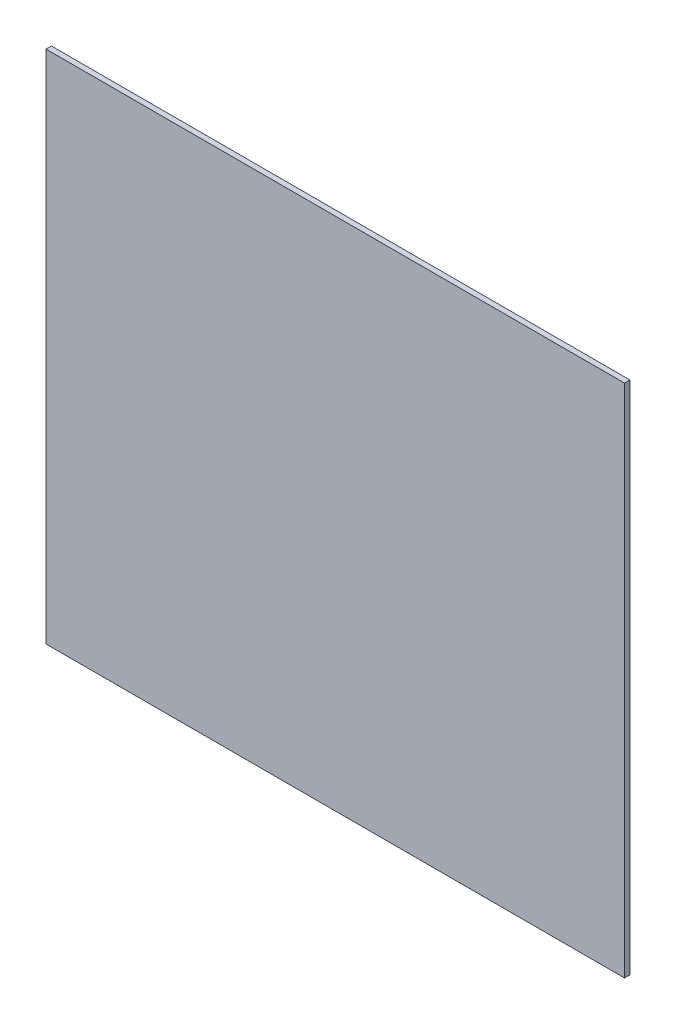
SolidWorks part; units mm, degrees
ref_plane "Front Plane" through (0, 0, 0) normal (0, 0, 1) x (1, 0, 0)
ref_plane "Top Plane" through (0, 0, 0) normal (0, 1, 0) x (1, 0, 0)
ref_plane "Right Plane" through (0, 0, 0) normal (1, 0, 0) x (0, 0, -1)
sketch "Sketch1" plane through (0, 0, 0) normal (0, 0, 1) x (1, 0, 0)
  line L1 (-160, -142.5) -> (160, -142.5)
  line L2 (-160, -142.5) -> (-160, 142.5)
  line L3 (-160, 142.5) -> (160, 142.5)
  line L4 (160, -142.5) -> (160, 142.5)
  line L5 (-160, -142.5) -> (160, 142.5) construction
  line L6 (-160, 142.5) -> (160, -142.5) construction
  point P0 (0, 0)
  dimension "D1" = 285
  dimension "D2" = 320
extrude "Boss-Extrude1" add sketch "Sketch1" along normal blind 3
equation "\"PCWidth\"= 172mm"
equation "\"PCLength\"= 320mm"
equation "\"PCHeight\"= 242mm"
equation "\"WallThickness\"= 9mm"
equation "\"ThermoBarrierThickness\"= 3mm"
equation "\"HotSideGap\"= 50mm"
equation "\"PCClearance\"= 25mm"
equation "\"RadiatorHeight\"= 275mm"
equation "\"D1@Sketch1\"=\"RadiatorHeight\" + 10"
equation "\"D2@Sketch1\"=\"PCLength\""
equation "\"D1@Boss-Extrude1\"=\"ThermoBarrierThickness\""
